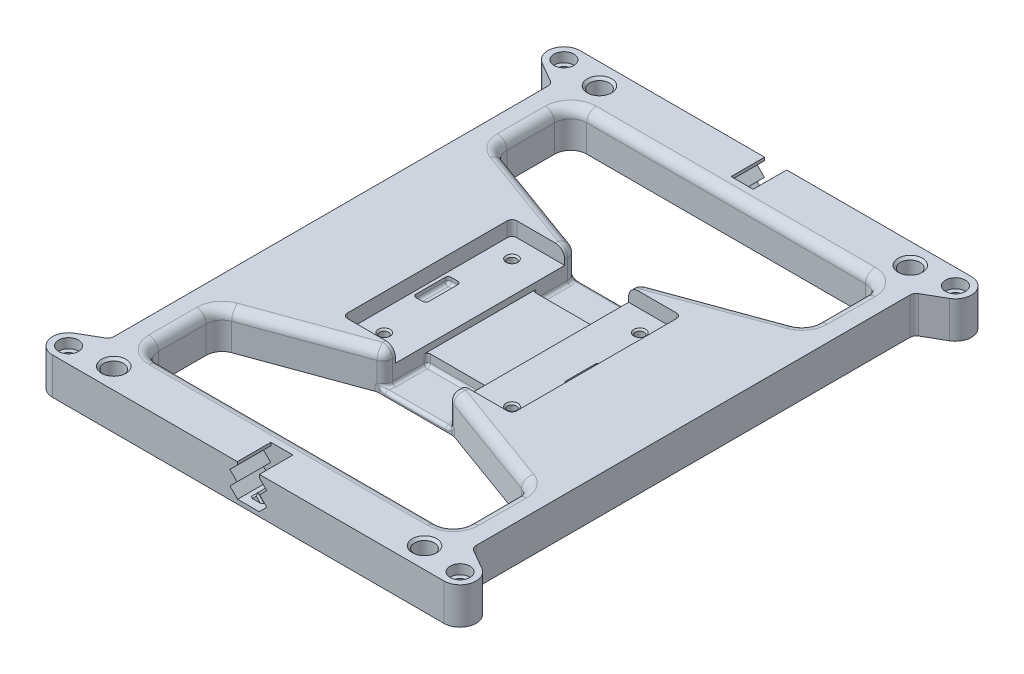
SolidWorks part; units mm, degrees
ref_plane "Front Plane" through (0, 0, 0) normal (0, 0, 1) x (1, 0, 0)
ref_plane "Top Plane" through (0, 0, 0) normal (0, 1, 0) x (1, 0, 0)
ref_plane "Right Plane" through (0, 0, 0) normal (1, 0, 0) x (0, 0, -1)
sketch "Sketch1" plane through (0, 0, 0) normal (0, 1, 0) x (1, 0, 0)
  line L0 (0, 0) -> (0, 67.5) construction
  line L1 (0, 67.5) -> (-56.625, 67.5) construction
  line L2 (-56.625, 67.5) -> (-56.625, 0)
  line L3 (-56.625, 0) -> (56.625, 0)
  line L4 (-56.625, 67.5) -> (-56.625, 80.5)
  line L5 (-54.625, 82.5) -> (54.625, 82.5)
  line L6 (0, 82.5) -> (0, 67.5) construction
  line L9 (56.625, 67.5) -> (56.625, 80.5)
  line L10 (56.625, 67.5) -> (56.625, 0)
  line L14 (-56.625, 70.5) -> (0, 70.5) construction
  circle A1 centre (-48.625, 76) radius 3.075 construction
  arc A11 (-56.625, 80.5) -> (-54.625, 82.5) centre (-54.625, 80.5) cw
  circle A12 centre (48.625, 76) radius 3.075 construction
  arc A13 (56.625, 80.5) -> (54.625, 82.5) centre (54.625, 80.5) ccw
  point P19 (56.625, 82.5)
  point P45 (-56.625, 82.5)
  dimension "D5" = 12
  dimension "D3" = 6.15
  dimension "D4" = 2
  dimension "D1" = 56.625
  dimension "D2" = 67.5
  dimension "D6" = 8
  dimension "D7" = 8.5
  dimension "D8" = 3
  dimension "D11" = 82.5
extrude "Boss-Extrude1" add sketch "Sketch1" along normal blind 11.5
sketch "Sketch3" plane through (0, 11.5, 0) normal (0, 1, 0) x (1, 0, 0)
  line L0 (0, 0) -> (-56.625, 0) construction
  line L2 (0, 0) -> (0, 82.5) construction
  line L3 (54.625, 82.5) -> (-54.625, 82.5) construction
  line L4 (3.96, -16.3) -> (3.96, 16.3)
  line L5 (-2.46, -17.8) -> (2.46, -17.8)
  line L6 (-3.96, 16.3) -> (-3.96, -16.3)
  line L7 (2.46, 17.8) -> (-2.46, 17.8)
  line L8 (0, 17.8) -> (0, -17.8) construction
  line L9 (-56.625, 80.5) -> (-56.625, 0) construction
  line L10 (-56.625, 0) -> (56.625, 0) construction
  arc A0 (-2.46, 17.8) -> (-3.96, 16.3) centre (-2.46, 16.3) ccw
  arc A1 (3.96, 16.3) -> (2.46, 17.8) centre (2.46, 16.3) ccw
  arc A2 (2.46, -17.8) -> (3.96, -16.3) centre (2.46, -16.3) ccw
  arc A3 (-3.96, -16.3) -> (-2.46, -17.8) centre (-2.46, -16.3) ccw
  point P9 (0, 0)
  point P23 (0, 0)
  dimension "D2" = 1.5
  dimension "D1" = 35.6
  dimension "D3" = 7.92
sketch "Sketch4" plane through (0, 11.5, 0) normal (0, 1, 0) x (1, 0, 0)
  circle A3 centre (48.625, 76) radius 3.075 construction
  circle A5 centre (-48.625, 76) radius 3.075 construction
  circle A10 centre (48.625, 76) radius 3.075
  circle A13 centre (-48.625, 76) radius 3.075
extrude "Cut-Extrude1" cut sketch "Sketch4" against normal blind 6
sketch "Sketch40" plane through (0, 0, -82.5) normal (0, 0, -1) x (-1, 0, 0)
  line L1 (5.55, 3.75) -> (3.3, 6) construction
  line L2 (5.55, 3.75) -> (3.3, 1.5) construction
  line L3 (0, 11.5) -> (0, 1.5) construction
  line L4 (0, 1.5) -> (3.3, 1.5) construction
  line L5 (3.3, 6) -> (5.55, 8.25) construction
  line L6 (3.3, 6) -> (3.3, 1.5) construction
  line L7 (5.55, 8.25) -> (3.3, 10.5) construction
  line L8 (3.3, 6) -> (3.3, 10.5) construction
  line L9 (5.55, 3.75) -> (5.55, 8.25) construction
  line L10 (3.3, 10.5) -> (3.3, 11.5) construction
  line L11 (3.3, 1.5) -> (5.55, 1.5) construction
  line L12 (5.55, 1.5) -> (5.55, 3.75) construction
  line L13 (5.55, 3.75) -> (3.3, 3.75) construction
  line L14 (5.55, 8.25) -> (3.3, 8.25) construction
  line L15 (3.3, 6) -> (5.55, 6) construction
  line L16 (-3.3, 11.5) -> (3.3, 11.5)
  line L17 (3.3621, 1.35) -> (-3.3621, 1.35)
  line L18 (0, 1.35) -> (0, 1.5) construction
  line L19 (-3.3, 11.5) -> (-3.45, 11.5)
  line L20 (-3.45, 10.5621) -> (-3.45, 11.5)
  line L22 (3.45, 10.5621) -> (3.45, 11.5)
  line L23 (5.7621, 8.25) -> (3.45, 10.5621)
  line L24 (3.5121, 6) -> (5.7621, 8.25)
  line L25 (5.7621, 3.75) -> (3.5121, 6)
  line L26 (5.7621, 3.75) -> (3.3621, 1.35)
  line L33 (3.3, 11.5) -> (3.45, 11.5)
  line L34 (-54.625, 11.5) -> (54.625, 11.5) construction
  line L35 (-5.7621, 8.25) -> (-3.45, 10.5621)
  line L36 (-3.5121, 6) -> (-5.7621, 8.25)
  line L37 (-5.7621, 3.75) -> (-3.5121, 6)
  line L38 (-5.7621, 3.75) -> (-3.3621, 1.35)
  dimension "D2" = 1
  dimension "D3" = 45
  dimension "D4" = 45
  dimension "D5" = 45
  dimension "D6" = 45
  dimension "D7" = 3.3
  dimension "D1" = 10
  dimension "D8" = 0.15
  dimension "D9" = 0.15
  dimension "D10" = 0.15
  dimension "D11" = 0.15
  dimension "D12" = 0.15
  dimension "D13" = 0.15
extrude "Cut-Extrude31" cut sketch "Sketch40" against normal blind 10.5
sketch "Sketch41" plane through (0, 0, -72) normal (0, 0, -1) x (-1, 0, 0)
  line L0 (0, 1.35) -> (0, 3.35) construction
  line L1 (-3.3621, 1.35) -> (3.3621, 1.35) construction
  line L2 (0, 3.35) -> (2, 1.35)
  line L3 (-3.3621, 1.35) -> (3.3621, 1.35) construction
  line L4 (2, 1.35) -> (-2, 1.35)
  line L5 (0, 3.35) -> (-2, 1.35)
  dimension "D1" = 45
  dimension "D2" = 2
extrude "Boss-Extrude9" add sketch "Sketch41" along normal blind 8
chamfer "Chamfer7" distance 0.5 angle 45 2 edges at (1, 2.35, -80) (-1, 2.35, -80)
mirror "Mirror1" about plane through (0, 0, 0) normal (0, 0, 1) of "Cut-Extrude1", "Boss-Extrude1", "Cut-Extrude31", "Boss-Extrude9", "Chamfer7"
sketch "Sketch28" plane through (0, 11.5, 0) normal (0, 1, 0) x (1, 0, 0)
  line L1 (-26, 26) -> (26, 26) construction
  line L2 (-26, 26) -> (-26, -26) construction
  line L3 (-26, -26) -> (26, -26) construction
  line L4 (26, 26) -> (26, -26) construction
  line L5 (-26, 26) -> (26, -26) construction
  line L6 (-26, -26) -> (26, 26) construction
  line L7 (-25, 26.5) -> (25, 26.5)
  line L8 (-26.5, 25) -> (-26.5, -25)
  line L9 (-25, -26.5) -> (25, -26.5)
  line L10 (26.5, 25) -> (26.5, -25)
  line L11 (-26.5, 26.5) -> (26.5, -26.5) construction
  line L12 (-26.5, -26.5) -> (26.5, 26.5) construction
  arc A0 (-25, -26.5) -> (-26.5, -25) centre (-25, -25) cw
  arc A1 (25, -26.5) -> (26.5, -25) centre (25, -25) ccw
  arc A2 (25, 26.5) -> (26.5, 25) centre (25, 25) cw
  arc A3 (-25, 26.5) -> (-26.5, 25) centre (-25, 25) ccw
  point P0 (0, 0)
  point P6 (0, 0)
  dimension "D4" = 1.5
  dimension "D1" = 52
  dimension "D2" = 0.5
  dimension "D3" = 0.5
extrude "Cut-Extrude21" cut sketch "Sketch28" against normal blind 4.6
sketch "Sketch36" plane through (0, 6.9, 0) normal (0, 1, 0) x (1, 0, 0)
  line L2 (-26, 26) -> (-26, -26) construction
  line L3 (-26, 26) -> (26, 26) construction
  circle A0 centre (-20, 20) radius 1.35
  circle A1 centre (20, 20) radius 1.35
  circle A2 centre (20, -20) radius 1.35
  circle A3 centre (-20, -20) radius 1.35
  point P15 (0, 0)
  dimension "D3" = 2.7
  dimension "D1" = 6
  dimension "D2" = 6
extrude "Cut-Extrude28" cut sketch "Sketch36" against normal blind 5
chamfer "Chamfer6" distance 0.5 angle 45 4 edges at (-20, 6.9, 21.35) (20, 6.9, 21.35) (20, 6.9, -18.65) (-20, 6.9, -18.65)
sketch "Sketch29" plane through (0, 6.9, 0) normal (0, 1, 0) x (1, 0, 0)
  line L0 (0, 0) -> (26.5, 0) construction
  line L5 (0, 0) -> (0, -26.5) construction
  line L6 (-25, -26.5) -> (25, -26.5) construction
  line L7 (26.5, -25) -> (26.5, 25) construction
  line L8 (-10, 26.5) -> (10, 16.5) construction
  line L9 (-10, 16.5) -> (10, 26.5) construction
  line L10 (-10, -16.5) -> (10, -16.5)
  line L11 (-10, -16.5) -> (-10, -26.5)
  line L12 (-10, -26.5) -> (10, -26.5)
  line L13 (10, -16.5) -> (10, -26.5)
  line L14 (-10, -16.5) -> (10, -26.5) construction
  line L15 (-10, -26.5) -> (10, -16.5) construction
  line L16 (10, 16.5) -> (10, 26.5)
  line L17 (-10, 26.5) -> (10, 26.5)
  line L18 (-10, 16.5) -> (-10, 26.5)
  line L19 (-10, 16.5) -> (10, 16.5)
  point P4 (0, -21.5)
  point P17 (0, 21.5)
  dimension "D1" = 20
  dimension "D2" = 10
extrude "Cut-Extrude22" cut sketch "Sketch29" against normal blind 5.5
sketch "Sketch25" plane through (0, 0, 0) normal (0, -1, 0) x (1, 0, 0)
  line L0 (0, 0) -> (56.625, 0) construction
  line L2 (0, 0) -> (0, 82.5) construction
  line L4 (63.75, 73.1699) -> (57.625, 69.6336)
  line L5 (61.25, 77.5) -> (56.625, 77.5) construction
  line L6 (56.625, 67.9016) -> (56.625, 80.5)
  line L8 (54.625, 82.5) -> (61.25, 82.5)
  line L9 (-61.25, 77.5) -> (-56.625, 77.5) construction
  line L10 (-54.625, 82.5) -> (-61.25, 82.5)
  line L11 (-56.625, 67.9016) -> (-56.625, 80.5)
  line L12 (-63.75, 73.1699) -> (-57.625, 69.6336)
  line L13 (-61.25, -77.5) -> (-56.625, -77.5) construction
  line L14 (61.25, -77.5) -> (56.625, -77.5) construction
  line L15 (-63.75, -73.1699) -> (-57.625, -69.6336)
  line L16 (-56.625, -67.9016) -> (-56.625, -80.5)
  line L17 (-54.625, -82.5) -> (-61.25, -82.5)
  line L18 (54.625, -82.5) -> (61.25, -82.5)
  line L19 (56.625, -67.9016) -> (56.625, -80.5)
  line L20 (63.75, -73.1699) -> (57.625, -69.6336)
  line L21 (56.625, 80.5) -> (56.625, -80.5) construction
  line L22 (54.625, 82.5) -> (-54.625, 82.5) construction
  circle A0 centre (61.25, 77.5) radius 1.7
  arc A1 (63.75, 73.1699) -> (61.25, 82.5) centre (61.25, 77.5) ccw
  arc A2 (57.625, 69.6336) -> (56.625, 67.9016) centre (58.625, 67.9016) ccw
  arc A17 (56.625, 80.5) -> (54.625, 82.5) centre (54.625, 80.5) ccw
  arc A18 (-56.625, 80.5) -> (-54.625, 82.5) centre (-54.625, 80.5) cw
  arc A19 (-57.625, 69.6336) -> (-56.625, 67.9016) centre (-58.625, 67.9016) cw
  arc A20 (-63.75, 73.1699) -> (-61.25, 82.5) centre (-61.25, 77.5) cw
  circle A21 centre (-61.25, 77.5) radius 1.7
  circle A22 centre (-61.25, -77.5) radius 1.7
  arc A23 (-63.75, -73.1699) -> (-61.25, -82.5) centre (-61.25, -77.5) ccw
  arc A24 (-57.625, -69.6336) -> (-56.625, -67.9016) centre (-58.625, -67.9016) ccw
  arc A25 (-56.625, -80.5) -> (-54.625, -82.5) centre (-54.625, -80.5) ccw
  arc A26 (56.625, -80.5) -> (54.625, -82.5) centre (54.625, -80.5) cw
  arc A27 (57.625, -69.6336) -> (56.625, -67.9016) centre (58.625, -67.9016) cw
  arc A28 (63.75, -73.1699) -> (61.25, -82.5) centre (61.25, -77.5) cw
  circle A29 centre (61.25, -77.5) radius 1.7
  arc A30 (56.625, 80.5) -> (54.625, 82.5) centre (54.625, 80.5) ccw construction
  dimension "D1" = 3.4
  dimension "D2" = 10
  dimension "D6" = 2
  dimension "D3" = 4.625
  dimension "D4" = 60
extrude "Boss-Extrude7" add sketch "Sketch25" against normal up to surface (11.5 mm away) up to face at (0, 11.5, 0)
sketch "Sketch27" plane through (0, 11.5, 0) normal (0, 1, 0) x (1, 0, 0)
  circle A4 centre (-61.25, -77.5) radius 3.1
  circle A5 centre (61.25, -77.5) radius 3.1
  circle A6 centre (-61.25, 77.5) radius 3.1
  circle A7 centre (61.25, 77.5) radius 3.1
  dimension "D1" = 6.2
extrude "Cut-Extrude20" cut sketch "Sketch27" against normal blind 3
sketch "Sketch37" plane through (0, 6.9, 0) normal (0, 1, 0) x (1, 0, 0)
  line L0 (56.625, 0) -> (0, 0) construction
  line L2 (0, 0) -> (-56.625, 0) construction
  line L3 (26.5, -25) -> (26.5, 25) construction
  line L4 (24.5, 5.5) -> (22.5, 5.5)
  line L5 (25.5, 4.5) -> (25.5, -4.5)
  line L6 (24.5, -5.5) -> (22.5, -5.5)
  line L7 (21.5, 4.5) -> (21.5, -4.5)
  line L8 (25.5, 5.5) -> (21.5, -5.5) construction
  line L9 (25.5, -5.5) -> (21.5, 5.5) construction
  line L10 (0, 0) -> (0, 26.5) construction
  line L11 (-10, 16.5) -> (10, 16.5) construction
  line L12 (-24.5, -5.5) -> (-22.5, -5.5)
  line L13 (-25.5, 4.5) -> (-25.5, -4.5)
  line L14 (-24.5, 5.5) -> (-22.5, 5.5)
  line L15 (-21.5, 4.5) -> (-21.5, -4.5)
  line L21 (10, 16.5) -> (10, -16.5)
  line L23 (25, 26.5) -> (-25, 26.5) construction
  line L24 (-10, 16.5) -> (10, 16.5)
  line L25 (-10, 16.5) -> (-10, -16.5)
  line L26 (-10, -16.5) -> (10, -16.5)
  line L27 (56.625, -67.9016) -> (56.625, 67.9016) construction
  arc A0 (22.5, -5.5) -> (21.5, -4.5) centre (22.5, -4.5) cw
  arc A1 (25.5, -4.5) -> (24.5, -5.5) centre (24.5, -4.5) cw
  arc A2 (22.5, 5.5) -> (21.5, 4.5) centre (22.5, 4.5) ccw
  arc A3 (24.5, 5.5) -> (25.5, 4.5) centre (24.5, 4.5) cw
  arc A4 (-22.5, 5.5) -> (-21.5, 4.5) centre (-22.5, 4.5) cw
  arc A5 (-24.5, 5.5) -> (-25.5, 4.5) centre (-24.5, 4.5) ccw
  arc A6 (-22.5, -5.5) -> (-21.5, -4.5) centre (-22.5, -4.5) ccw
  arc A7 (-25.5, -4.5) -> (-24.5, -5.5) centre (-24.5, -4.5) ccw
  point P5 (23.5, 0)
  point P54 (10, 0)
  point P56 (-10, 0)
  dimension "D4" = 1
  dimension "D1" = 11
  dimension "D2" = 4
  dimension "D3" = 3
extrude "Cut-Extrude29" cut sketch "Sketch37" against normal blind 2
fillet "Fillet20" radius 1 16 edges at (25.2071, 4.9, -5.2071) (25.5, 4.9, 0) (25.2071, 4.9, 5.2071) (23.5, 4.9, 5.5) (21.7929, 4.9, 5.2071) (21.5, 4.9, 0) (21.7929, 4.9, -5.2071) (-21.7929, 4.9, -5.2071) (-21.5, 4.9, 0) (-21.7929, 4.9, 5.2071) (-23.5, 4.9, 5.5) (-25.2071, 4.9, 5.2071) (-25.5, 4.9, 0) (-25.2071, 4.9, -5.2071) (23.5, 4.9, -5.5) (-23.5, 4.9, -5.5)
sketch "Sketch38" plane through (0, 11.5, 0) normal (0, 1, 0) x (1, 0, 0)
  line L0 (11.9739, -30.2185) -> (45.3351, -42.3609)
  line L1 (48.625, -47.0594) -> (48.625, -62)
  line L2 (43.625, -67) -> (-43.625, -67)
  line L3 (0, -67) -> (0, -26.5) construction
  line L4 (-10, -26.5) -> (10, -26.5) construction
  line L7 (-3.45, -72) -> (3.45, -72) construction
  line L9 (-25, -26.5) -> (25, -26.5) construction
  line L12 (0, 0) -> (56.625, 0) construction
  line L13 (0, 67) -> (0, 26.5) construction
  line L20 (10, -27.3994) -> (10, -26.5)
  line L21 (10, -26.5) -> (25, -26.5) construction
  line L22 (10, -26.5) -> (-10, -26.5)
  line L23 (10, -26.5) -> (10, 26.5) construction
  line L24 (-10, -27.3994) -> (-10, -26.5)
  line L25 (-48.625, -47.0594) -> (-48.625, -62)
  line L26 (-11.9739, -30.2185) -> (-45.3351, -42.3609)
  line L35 (56.625, -67.9016) -> (56.625, 67.9016) construction
  line L36 (-11.9739, 30.2185) -> (-45.3351, 42.3609)
  line L37 (-48.625, 47.0594) -> (-48.625, 62)
  line L38 (-10, 27.3994) -> (-10, 26.5)
  line L39 (10, 26.5) -> (-10, 26.5)
  line L40 (10, 27.3994) -> (10, 26.5)
  line L41 (43.625, 67) -> (-43.625, 67)
  line L42 (48.625, 47.0594) -> (48.625, 62)
  line L43 (11.9739, 30.2185) -> (45.3351, 42.3609)
  arc A0 (48.625, -47.0594) -> (45.3351, -42.3609) centre (43.625, -47.0594) ccw
  arc A1 (48.625, -62) -> (43.625, -67) centre (43.625, -62) cw
  arc A8 (11.9739, -30.2185) -> (10, -27.3994) centre (13, -27.3994) cw
  arc A9 (-11.9739, -30.2185) -> (-10, -27.3994) centre (-13, -27.3994) ccw
  arc A10 (-48.625, -62) -> (-43.625, -67) centre (-43.625, -62) ccw
  arc A11 (-48.625, -47.0594) -> (-45.3351, -42.3609) centre (-43.625, -47.0594) cw
  arc A18 (-48.625, 47.0594) -> (-45.3351, 42.3609) centre (-43.625, 47.0594) ccw
  arc A19 (-48.625, 62) -> (-43.625, 67) centre (-43.625, 62) cw
  arc A20 (-11.9739, 30.2185) -> (-10, 27.3994) centre (-13, 27.3994) cw
  arc A21 (11.9739, 30.2185) -> (10, 27.3994) centre (13, 27.3994) ccw
  arc A22 (48.625, 62) -> (43.625, 67) centre (43.625, 62) ccw
  arc A23 (48.625, 47.0594) -> (45.3351, 42.3609) centre (43.625, 47.0594) cw
  point P49 (10, -29.5)
  point P60 (-10, -29.5)
  point P66 (-10, 29.5)
  point P67 (10, 29.5)
  dimension "D4" = 5
  dimension "D6" = 3
  dimension "D1" = 5
  dimension "D2" = 8
  dimension "D3" = 20
  dimension "D5" = 3
extrude "Cut-Extrude30" cut sketch "Sketch38" against normal through all
sketch "Sketch39" plane through (0, 0, 0) normal (0, -1, 0) x (1, 0, 0)
  line L0 (0, 0) -> (56.625, 0) construction
  line L2 (-11.9739, 30.2185) -> (11.9739, 30.2185)
  line L3 (10, 27.3994) -> (10, 26.5) construction
  line L4 (10, 26.5) -> (-10, 26.5) construction
  line L5 (-10, 26.5) -> (-10, 27.3994) construction
  line L6 (10, 27.3994) -> (10, 26.5)
  line L7 (10, 26.5) -> (-10, 26.5)
  line L8 (-10, 26.5) -> (-10, 27.3994)
  line L9 (-10, -26.5) -> (-10, -27.3994)
  line L10 (10, -26.5) -> (-10, -26.5)
  line L11 (10, -27.3994) -> (10, -26.5)
  line L12 (-11.9739, -30.2185) -> (11.9739, -30.2185)
  line L13 (56.625, 67.9016) -> (56.625, -67.9016) construction
  arc A0 (11.9739, 30.2185) -> (10, 27.3994) centre (13, 27.3994) ccw construction
  arc A1 (-10, 27.3994) -> (-11.9739, 30.2185) centre (-13, 27.3994) ccw construction
  arc A2 (11.9739, 30.2185) -> (10, 27.3994) centre (13, 27.3994) ccw
  arc A3 (-10, 27.3994) -> (-11.9739, 30.2185) centre (-13, 27.3994) ccw
  arc A4 (-10, -27.3994) -> (-11.9739, -30.2185) centre (-13, -27.3994) cw
  arc A5 (11.9739, -30.2185) -> (10, -27.3994) centre (13, -27.3994) cw
extrude "Boss-Extrude8" add sketch "Sketch39" against normal up to surface (1.4 mm away) up to face at (0, 1.4, 21.5)
fillet "Fillet21" radius 1 14 edges at (0, 1.4, -16.5) (0, 1.4, 16.5) (-10.5425, 1.4, 29.1201) (10.5425, 1.4, 29.1201) (-10, 3.15, 16.5) (-10, 1.4, 21.9497) (10, 3.15, 16.5) (10, 1.4, 21.9497) (-10, 1.4, -21.9497) (-10, 3.15, -16.5) (10, 3.15, -16.5) (10, 1.4, -21.9497) (-10.5425, 1.4, -29.1201) (10.5425, 1.4, -29.1201)
fillet "Fillet22" radius 3 26 edges at (-10, 11.5, 26.9497) (-10.5425, 11.5, 29.1201) (10, 11.5, 26.9497) (10.5425, 11.5, 29.1201) (28.6545, 11.5, 36.2897) (47.7208, 11.5, 44.1915) (48.625, 11.5, 54.5297) (47.1605, 11.5, 65.5355) (0, 11.5, 67) (-47.1605, 11.5, 65.5355) (-48.625, 11.5, 54.5297) (-47.7208, 11.5, 44.1915) (-28.6545, 11.5, 36.2897) (10, 11.5, -26.9497) (10.5425, 11.5, -29.1201) (28.6545, 11.5, -36.2897) (47.7208, 11.5, -44.1915) (48.625, 11.5, -54.5297) (47.1605, 11.5, -65.5355) (0, 11.5, -67) (-47.1605, 11.5, -65.5355) (-48.625, 11.5, -54.5297) (-47.7208, 11.5, -44.1915) (-10, 11.5, -26.9497) (-10.5425, 11.5, -29.1201) (-28.6545, 11.5, -36.2897)
fillet "Fillet24" radius 3 4 edges at (-11.9739, 1.2, 30.2185) (11.9739, 1.2, 30.2185) (11.9739, 1.2, -30.2185) (-11.9739, 1.2, -30.2185)
fillet "Fillet25" radius 1 10 edges at (0, 1.4, 30.2185) (0, 1.4, -30.2185) (12.1079, 2.1665, 30.2926) (10.8141, 1.4985, 30.2185) (-12.1976, 2.1847, 30.3144) (-10.9036, 1.5265, 30.2185) (-10.8141, 1.4985, -30.2185) (10.9036, 1.5265, -30.2185) (-12.1079, 2.1665, -30.2926) (12.1976, 2.1847, -30.3144)
chamfer "Chamfer8" distance 0.75 angle 45 4 edges at (-48.625, 11.5, 72.925) (48.625, 11.5, 72.925) (-48.625, 11.5, -72.925) (48.625, 11.5, -72.925)
equation "\"D3@Sketch28\"=\"D2@Sketch28\""
equation "\"D2@Sketch36\"=\"D1@Sketch36\""
equation "\"D9@Sketch40\"=\"D8@Sketch40\""
equation "\"D10@Sketch40\"=\"D8@Sketch40\""
equation "\"D11@Sketch40\"=\"D8@Sketch40\""
equation "\"D12@Sketch40\"=\"D8@Sketch40\""
equation "\"D13@Sketch40\"=\"D8@Sketch40\""
